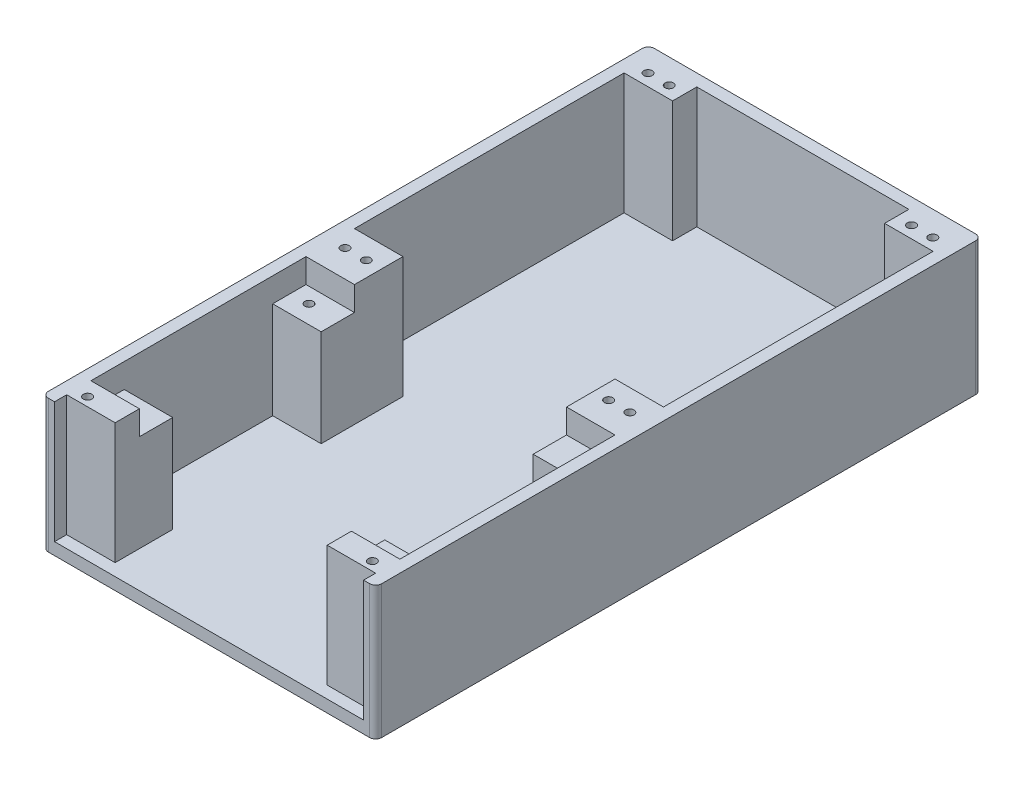
SolidWorks part; units mm, degrees
ref_plane "Front Plane" through (0, 0, 0) normal (0, 0, 1) x (1, 0, 0)
ref_plane "Top Plane" through (0, 0, 0) normal (0, 1, 0) x (1, 0, 0)
ref_plane "Right Plane" through (0, 0, 0) normal (1, 0, 0) x (0, 0, -1)
sketch "Sketch1" plane through (0, 0, 0) normal (0, 1, 0) x (1, 0, 0)
  line L1 (0, 0) -> (139.7, 0)
  line L2 (0, 0) -> (0, 254)
  line L3 (0, 254) -> (139.7, 254)
  line L4 (139.7, 0) -> (139.7, 254)
  dimension "D1" = 254
  dimension "D2" = 139.7
extrude "Base" add sketch "Sketch1" along normal blind 5.08
sketch "Sketch2" plane through (0, 5.08, 0) normal (0, 1, 0) x (1, 0, 0)
  line L1 (0, 254) -> (139.7, 254)
  line L2 (0, 254) -> (0, 0)
  line L3 (0, 0) -> (139.7, 0)
  line L4 (139.7, 254) -> (139.7, 0)
  line L5 (5.08, 248.92) -> (134.62, 248.92)
  line L6 (5.08, 248.92) -> (5.08, 5.08)
  line L7 (5.08, 5.08) -> (134.62, 5.08)
  line L8 (134.62, 248.92) -> (134.62, 5.08)
  line M9 (0, 254) -> (0, 0)
  line M10 (0, 0) -> (139.7, 0)
  line M11 (139.7, 0) -> (139.7, 254)
  line M12 (139.7, 254) -> (0, 254)
  dimension "D1" = 5.08
  dimension "D2" = 5.08
  dimension "D3" = 5.08
  dimension "D4" = 5.08
extrude "Walls" add sketch "Sketch2" along normal blind 50.8 contours L5 L8 L7 L6 M12 M9 M10 M11 region at (69.85, 5.08, -251.1012)
ref_plane "Plane1" through (0, 0, -60.96) normal (0, 0, 1) x (1, 0, 0)
sketch "Sketch4" plane through (0, 0, 0) normal (0, 0, 1) x (1, 0, 0)
  line L0 (0, 0) -> (139.7, 0) construction
  line L1 (5.08, 55.88) -> (134.62, 55.88)
  line L2 (5.08, 55.88) -> (5.08, 5.08)
  line L3 (5.08, 5.08) -> (134.62, 5.08)
  line L4 (134.62, 55.88) -> (134.62, 5.08)
  line L5 (0, 55.88) -> (0, 0) construction
  line L6 (139.7, 55.88) -> (139.7, 0) construction
  line L7 (0, 55.88) -> (139.7, 55.88) construction
  dimension "D1" = 5.08
  dimension "D2" = 5.08
  dimension "D3" = 5.08
  dimension "D4" = 0
extrude "Bottom Cut" cut sketch "Sketch4" against normal blind 139.7
sketch "Sketch12" plane through (0, 5.08, 0) normal (0, 1, 0) x (1, 0, 0)
  line L0 (139.7, 254) -> (0, 254) construction
  line L1 (134.62, 248.92) -> (114.3, 248.92)
  line L2 (134.62, 248.92) -> (134.62, 238.76)
  line L3 (134.62, 238.76) -> (114.3, 238.76)
  line L4 (114.3, 248.92) -> (114.3, 238.76)
  line L5 (139.7, 0) -> (139.7, 254) construction
  line L7 (5.08, 248.92) -> (25.4, 248.92)
  line L8 (5.08, 248.92) -> (5.08, 238.76)
  line L9 (5.08, 238.76) -> (25.4, 238.76)
  line L10 (25.4, 248.92) -> (25.4, 238.76)
  line L11 (134.62, 105.41) -> (114.3, 105.41)
  line L12 (134.62, 105.41) -> (134.62, 125.73)
  line L13 (134.62, 125.73) -> (114.3, 125.73)
  line L14 (114.3, 105.41) -> (114.3, 125.73)
  line L15 (5.08, 105.41) -> (25.4, 105.41)
  line L16 (5.08, 105.41) -> (5.08, 125.73)
  line L17 (5.08, 125.73) -> (25.4, 125.73)
  line L18 (25.4, 105.41) -> (25.4, 125.73)
  dimension "D1" = 15.24
  dimension "D2" = 25.4
  dimension "D3" = 20.32
extrude "Mounting Struts" add sketch "Sketch12" along normal up to surface (50.8 mm away) up to face at (69.85, 55.88, -125.73)
sketch "Sketch13" plane through (0, 55.88, 0) normal (0, 1, 0) x (1, 0, 0)
  line L0 (139.7, 254) -> (0, 254) construction
  line L1 (139.7, 0) -> (139.7, 254) construction
  circle A0 centre (120.65, 243.713) radius 1.778
  circle A1 centre (19.05, 243.713) radius 1.778
  circle A2 centre (120.65, 116.713) radius 1.778
  circle A3 centre (19.05, 116.713) radius 1.778
  dimension "D1" = 3.556
  dimension "D2" = 10.287
  dimension "D3" = 19.05
  dimension "D4" = 101.6
  dimension "D5" = 127
extrude "Panel Mounting Holes" cut sketch "Sketch13" against normal blind 12.7
sketch "Sketch14" plane through (0, 53.848, 0) normal (0, 1, 0) x (1, 0, 0)
  line L1 (134.62, 5.08) -> (114.3, 5.08)
  line L2 (134.62, 5.08) -> (134.62, 15.24)
  line L3 (134.62, 15.24) -> (114.3, 15.24)
  line L4 (114.3, 5.08) -> (114.3, 15.24)
  line L5 (5.08, 5.08) -> (25.4, 5.08)
  line L6 (5.08, 5.08) -> (5.08, 15.24)
  line L7 (5.08, 15.24) -> (25.4, 15.24)
  line L8 (25.4, 5.08) -> (25.4, 15.24)
  dimension "D1" = 10.16
  dimension "D2" = 20.32
extrude "Boss-Extrude6" add sketch "Sketch14" along normal up to surface and the other way up to surface up to face at (19.05, 55.88, -241.935) other way up to face at (69.85, 5.08, -148.59)
sketch "Sketch17" plane through (0, 55.88, 0) normal (0, 1, 0) x (1, 0, 0)
  line L0 (139.7, 0) -> (139.7, 254) construction
  line L1 (0, -30.734) -> (0, 30.734) construction
  circle A0 centre (129.54, 243.713) radius 1.778
  circle A1 centre (10.16, 243.713) radius 1.778
  circle A2 centre (10.16, 116.713) radius 1.778
  circle A3 centre (129.54, 116.713) radius 1.778
  circle A4 centre (129.54, 8.763) radius 1.778
  circle A5 centre (10.16, 8.763) radius 1.778
  circle A7 centre (120.65, 116.713) radius 1.778 construction
  circle A8 centre (19.05, 116.713) radius 1.778 construction
  circle A9 centre (19.05, 243.713) radius 1.778 construction
  circle A10 centre (120.65, 243.713) radius 1.778 construction
  dimension "D1" = 3.556
  dimension "D2" = 10.16
  dimension "D3" = 10.16
  dimension "D4" = 127
  dimension "D5" = 107.95
extrude "Front Mounting Holes" cut sketch "Sketch17" against normal blind 12.7
fillet "Corner Fillet" radius 2.54 4 edges at (0, 27.94, 0) (139.7, 27.94, 0) (0, 27.94, -254) (139.7, 27.94, -254)
sketch "Sketch18" plane through (0, 5.08, 0) normal (0, 1, 0) x (1, 0, 0)
  line L0 (25.4, 105.41) -> (25.4, 125.73) construction
  line L1 (5.08, 105.41) -> (25.4, 105.41)
  line L2 (5.08, 105.41) -> (5.08, 91.44)
  line L3 (5.08, 91.44) -> (25.4, 91.44)
  line L4 (25.4, 105.41) -> (25.4, 91.44)
  line L5 (134.62, 105.41) -> (114.3, 105.41)
  line L6 (134.62, 105.41) -> (134.62, 91.44)
  line L7 (134.62, 91.44) -> (114.3, 91.44)
  line L8 (114.3, 105.41) -> (114.3, 91.44)
  line L9 (134.62, 15.24) -> (114.3, 15.24)
  line L10 (134.62, 15.24) -> (134.62, 29.21)
  line L11 (134.62, 29.21) -> (114.3, 29.21)
  line L12 (114.3, 15.24) -> (114.3, 29.21)
  line L13 (5.08, 15.24) -> (25.4, 15.24)
  line L14 (5.08, 15.24) -> (5.08, 29.21)
  line L15 (5.08, 29.21) -> (25.4, 29.21)
  line L16 (25.4, 15.24) -> (25.4, 29.21)
  line L17 (114.3, 125.73) -> (114.3, 105.41) construction
  dimension "D1" = 13.97
extrude "Boss-Extrude8" add sketch "Sketch18" along normal blind 40.64
sketch "Sketch19" plane through (0, 45.72, 0) normal (0, 1, 0) x (1, 0, 0)
  line L0 (114.3, 105.41) -> (134.62, 105.41) construction
  line L1 (134.62, 105.41) -> (134.62, 15.24) construction
  line L2 (5.08, 15.24) -> (25.4, 15.24) construction
  line L3 (5.08, 105.41) -> (5.08, 15.24) construction
  circle A0 centre (12.7, 99.06) radius 1.778
  circle A1 centre (127, 99.06) radius 1.778
  circle A2 centre (127, 21.59) radius 1.778
  circle A3 centre (12.7, 21.59) radius 1.778
  point P8 (0, 0)
  point P9 (0, 0)
  point P10 (0, 0)
  point P11 (0, 0)
  point P12 (0, 0)
  dimension "D1" = 3.556
  dimension "D2" = 6.35
  dimension "D3" = 7.62
  dimension "D4" = 6.35
  dimension "D5" = 7.62
extrude "Cut-Extrude1" cut sketch "Sketch19" against normal blind 12.7
equation "\"Arrow Height\"= 1.5in"
equation "\"Button Height\"= 2in"
equation "\"Button Width\"= 4in"
equation "\"Haptic Diameter\"= 10mm"
equation "\"Haptic Thickness\"= 2.7mm"
equation "\"Arrow Spacing\"= 1in"
equation "\"Arrow Width\"= 1in"
equation "\"Haptic Wire Angle\"= 63.43"
equation "\"Haptic Wire Width\"= .1in"
equation "\"Haptic Wire Height\"= .15in"
equation "\"Mounting Bolt Hole Diameter\"= .14in"
equation "\"D1@Sketch13\"=\"Mounting Bolt Hole Diameter\""
equation "\"D1@Sketch17\"=\"Mounting Bolt Hole Diameter\""
equation "\"D1@Sketch19\"=\"Mounting Bolt Hole Diameter\""
